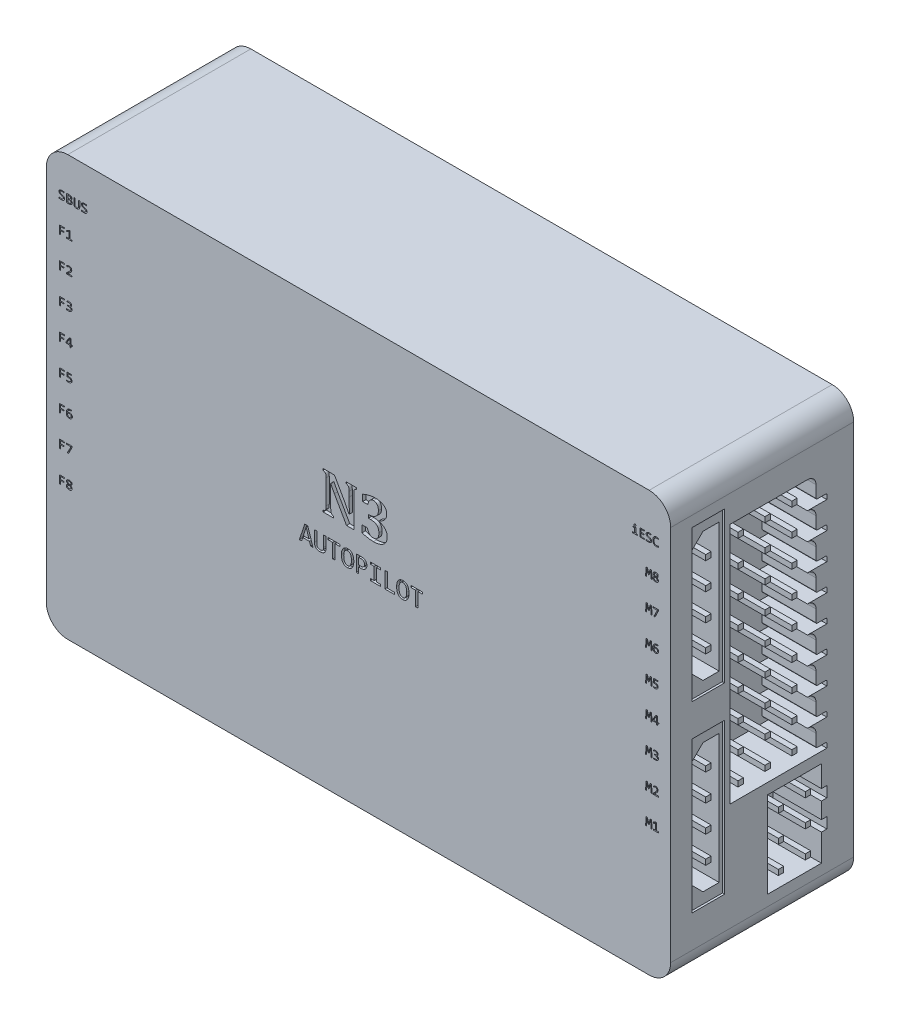
SolidWorks part; units mm, degrees
ref_plane "前视基准面" through (0, 0, 0) normal (0, 0, 1) x (1, 0, 0)
ref_plane "上视基准面" through (0, 0, 0) normal (0, 1, 0) x (1, 0, 0)
ref_plane "右视基准面" through (0, 0, 0) normal (1, 0, 0) x (0, 0, -1)
sketch "Main" plane through (0, 0, 0) normal (0, 0, 1) x (1, 0, 0)
  line L0 (-29, 17.5) -> (-29, -17.5)
  line L1 (0, 0) -> (30.1154, 0) construction
  line L2 (0, -7.3749) -> (0, 9.6594) construction
  line L3 (-27, 19.5) -> (27, 19.5)
  line L4 (29, 17.5) -> (29, -17.5)
  line L5 (-27, -19.5) -> (27, -19.5)
  arc A0 (-29, 17.5) -> (-27, 19.5) centre (-27, 17.5) cw
  arc A1 (29, 17.5) -> (27, 19.5) centre (27, 17.5) ccw
  arc A2 (29, -17.5) -> (27, -19.5) centre (27, -17.5) cw
  arc A3 (-29, -17.5) -> (-27, -19.5) centre (-27, -17.5) ccw
  point P6 (-29, 0)
  point P12 (0, 19.5)
  dimension "D2" = 2
  dimension "D1" = 29
  dimension "D4" = 19.5
extrude "Main_P" add sketch "Main" along normal mid plane 17
sketch "草图3" plane through (0, 0, 8.5) normal (0, 0, 1) x (1, 0, 0)
  line L0 (0, 0) -> (18.2534, 0) construction
  line L1 (0, 0) -> (0, 13.6083) construction
  text T0 "N3" font "Cambria" height 3.5
  text T1 "AUTOPILOT" font "Consolas" height 1.5
  dimension "D1" = 3.55
  dimension "D2" = 5.5
extrude "Font" cut sketch "草图3" against normal blind 0.3
sketch "PAM_Interface" plane through (-29, 0, 0) normal (-1, 0, 0) x (0, 0, 1)
  line L0 (-15.3995, 0) -> (15.3995, 0) construction
  line L1 (0, 21.507) -> (0, -21.507) construction
  line L2 (-2.9542, 2.4634) -> (6.0458, 2.4634)
  line L3 (2.0458, 1.7134) -> (2.0458, 0.7134)
  line L4 (6.0458, 2.4634) -> (6.0458, -0.0366)
  line L5 (6.0458, -0.0366) -> (-1.6542, -0.0366)
  line L6 (-2.8542, 1.9634) -> (-2.0542, 1.9634)
  line L7 (-2.9542, 2.4634) -> (-2.9542, 2.0634)
  line L8 (4.5458, 1.7134) -> (5.5458, 1.7134)
  line L9 (-1.9542, 1.8634) -> (-1.9542, 0.2634)
  line L10 (4.5458, 1.7134) -> (4.5458, 0.7134)
  line L11 (4.5458, 0.7134) -> (5.5458, 0.7134)
  line L12 (5.5458, 1.7134) -> (5.5458, 0.7134)
  line L13 (2.0458, 1.7134) -> (3.0458, 1.7134)
  line L14 (3.0458, 1.7134) -> (3.0458, 0.7134)
  line L15 (2.0458, 0.7134) -> (3.0458, 0.7134)
  line L16 (-0.4542, 1.7134) -> (-0.4542, 0.7134)
  line L17 (-0.4542, 1.7134) -> (0.5458, 1.7134)
  line L18 (0.5458, 1.7134) -> (0.5458, 0.7134)
  line L19 (-0.4542, 0.7134) -> (0.5458, 0.7134)
  arc A0 (-2.9542, 2.0634) -> (-2.8542, 1.9634) centre (-2.8542, 2.0634) ccw
  arc A1 (-1.6542, -0.0366) -> (-1.9542, 0.2634) centre (-1.6542, 0.2634) cw
  arc A2 (-1.9542, 1.8634) -> (-2.0542, 1.9634) centre (-2.0542, 1.8634) ccw
  dimension "D3" = 2.5
  dimension "D4" = 0.3
  dimension "D1" = 0.1
  dimension "D5" = 0.1
  dimension "D2" = 0.5
  dimension "D6" = 1
  dimension "D7" = 1
  dimension "D8" = 0.75
  dimension "D9" = 0.5
  dimension "D10" = 8
  dimension "D11" = 3
sketch "SBus" plane through (-29, 0, 0) normal (-1, 0, 0) x (0, 0, 1)
  line L0 (8.5, 9.91) -> (8.5, 21.1586) construction
  line L1 (-7.8997, 19.5) -> (7.3159, 19.5) construction
  line B0 (-6, 16.5) -> (3, 16.5)
  line B1 (3, 16.5) -> (3, 14)
  line B2 (3, 14) -> (-4.2, 14)
  line B3 (-5.9, 16) -> (-5.1, 16)
  line B4 (-6, 16.5) -> (-6, 16.1)
  line B5 (1.75, 15.5) -> (2.25, 15.5)
  line B6 (-5, 15.9) -> (-5, 14.8)
  line B7 (1.75, 15.5) -> (1.75, 15)
  line B8 (1.75, 15) -> (2.25, 15)
  line B9 (2.25, 15.5) -> (2.25, 15)
  line B10 (-0.75, 15.5) -> (-0.25, 15.5)
  line B11 (-0.25, 15.5) -> (-0.25, 15)
  line B12 (-0.75, 15) -> (-0.25, 15)
  line B13 (-0.75, 15.5) -> (-0.75, 15)
  line B14 (-3.25, 15.5) -> (-2.75, 15.5)
  line B15 (-2.75, 15.5) -> (-2.75, 15)
  line B16 (-3.25, 15) -> (-2.75, 15)
  line B17 (-3.25, 15.5) -> (-3.25, 15)
  line B18 (1.75, 15.5) -> (-0.75, 15.5) construction
  line B19 (-6, 14) -> (3, 14)
  line B20 (3, 14) -> (3, 11.5)
  line B21 (3, 11.5) -> (-4.2, 11.5)
  line B22 (-5, 13.4) -> (-5, 12.3)
  line B23 (-5.9, 13.5) -> (-5.1, 13.5)
  line B24 (-6, 14) -> (-6, 13.6)
  line B25 (-3.25, 13) -> (-2.75, 13)
  line B26 (-2.75, 13) -> (-2.75, 12.5)
  line B27 (-3.25, 12.5) -> (-2.75, 12.5)
  line B28 (-3.25, 13) -> (-3.25, 12.5)
  line B29 (-0.75, 13) -> (-0.25, 13)
  line B30 (-0.25, 13) -> (-0.25, 12.5)
  line B31 (-0.75, 12.5) -> (-0.25, 12.5)
  line B32 (-0.75, 13) -> (-0.75, 12.5)
  line B33 (1.75, 13) -> (2.25, 13)
  line B34 (2.25, 13) -> (2.25, 12.5)
  line B35 (1.75, 12.5) -> (2.25, 12.5)
  line B36 (1.75, 13) -> (1.75, 12.5)
  line B37 (-6, 11.5) -> (3, 11.5)
  line B38 (3, 11.5) -> (3, 9)
  line B39 (3, 9) -> (-4.2, 9)
  line B40 (-5, 10.9) -> (-5, 9.8)
  line B41 (-5.9, 11) -> (-5.1, 11)
  line B42 (-6, 11.5) -> (-6, 11.1)
  line B43 (-3.25, 10.5) -> (-2.75, 10.5)
  line B44 (-2.75, 10.5) -> (-2.75, 10)
  line B45 (-3.25, 10) -> (-2.75, 10)
  line B46 (-3.25, 10.5) -> (-3.25, 10)
  line B47 (-0.75, 10.5) -> (-0.25, 10.5)
  line B48 (-0.25, 10.5) -> (-0.25, 10)
  line B49 (-0.75, 10) -> (-0.25, 10)
  line B50 (-0.75, 10.5) -> (-0.75, 10)
  line B51 (1.75, 10.5) -> (2.25, 10.5)
  line B52 (2.25, 10.5) -> (2.25, 10)
  line B53 (1.75, 10) -> (2.25, 10)
  line B54 (1.75, 10.5) -> (1.75, 10)
  line B55 (-6, 9) -> (3, 9)
  line B56 (3, 9) -> (3, 6.5)
  line B57 (3, 6.5) -> (-4.2, 6.5)
  line B58 (-5, 8.4) -> (-5, 7.3)
  line B59 (-5.9, 8.5) -> (-5.1, 8.5)
  line B60 (-6, 9) -> (-6, 8.6)
  line B61 (-3.25, 8) -> (-2.75, 8)
  line B62 (-2.75, 8) -> (-2.75, 7.5)
  line B63 (-3.25, 7.5) -> (-2.75, 7.5)
  line B64 (-3.25, 8) -> (-3.25, 7.5)
  line B65 (-0.75, 8) -> (-0.25, 8)
  line B66 (-0.25, 8) -> (-0.25, 7.5)
  line B67 (-0.75, 7.5) -> (-0.25, 7.5)
  line B68 (-0.75, 8) -> (-0.75, 7.5)
  line B69 (1.75, 8) -> (2.25, 8)
  line B70 (2.25, 8) -> (2.25, 7.5)
  line B71 (1.75, 7.5) -> (2.25, 7.5)
  line B72 (1.75, 8) -> (1.75, 7.5)
  line B73 (-6, 6.5) -> (3, 6.5)
  line B74 (3, 6.5) -> (3, 4)
  line B75 (3, 4) -> (-4.2, 4)
  line B76 (-5, 5.9) -> (-5, 4.8)
  line B77 (-5.9, 6) -> (-5.1, 6)
  line B78 (-6, 6.5) -> (-6, 6.1)
  line B79 (-3.25, 5.5) -> (-2.75, 5.5)
  line B80 (-2.75, 5.5) -> (-2.75, 5)
  line B81 (-3.25, 5) -> (-2.75, 5)
  line B82 (-3.25, 5.5) -> (-3.25, 5)
  line B83 (-0.75, 5.5) -> (-0.25, 5.5)
  line B84 (-0.25, 5.5) -> (-0.25, 5)
  line B85 (-0.75, 5) -> (-0.25, 5)
  line B86 (-0.75, 5.5) -> (-0.75, 5)
  line B87 (1.75, 5.5) -> (2.25, 5.5)
  line B88 (2.25, 5.5) -> (2.25, 5)
  line B89 (1.75, 5) -> (2.25, 5)
  line B90 (1.75, 5.5) -> (1.75, 5)
  line B91 (-6, 4) -> (3, 4)
  line B92 (3, 4) -> (3, 1.5)
  line B93 (3, 1.5) -> (-4.2, 1.5)
  line B94 (-5, 3.4) -> (-5, 2.3)
  line B95 (-5.9, 3.5) -> (-5.1, 3.5)
  line B96 (-6, 4) -> (-6, 3.6)
  line B97 (-3.25, 3) -> (-2.75, 3)
  line B98 (-2.75, 3) -> (-2.75, 2.5)
  line B99 (-3.25, 2.5) -> (-2.75, 2.5)
  line B100 (-3.25, 3) -> (-3.25, 2.5)
  line B101 (-0.75, 3) -> (-0.25, 3)
  line B102 (-0.25, 3) -> (-0.25, 2.5)
  line B103 (-0.75, 2.5) -> (-0.25, 2.5)
  line B104 (-0.75, 3) -> (-0.75, 2.5)
  line B105 (1.75, 3) -> (2.25, 3)
  line B106 (2.25, 3) -> (2.25, 2.5)
  line B107 (1.75, 2.5) -> (2.25, 2.5)
  line B108 (1.75, 3) -> (1.75, 2.5)
  line B109 (-6, 1.5) -> (3, 1.5)
  line B110 (3, 1.5) -> (3, -1)
  line B111 (3, -1) -> (-4.2, -1)
  line B112 (-5, 0.9) -> (-5, -0.2)
  line B113 (-5.9, 1) -> (-5.1, 1)
  line B114 (-6, 1.5) -> (-6, 1.1)
  line B115 (-3.25, 0.5) -> (-2.75, 0.5)
  line B116 (-2.75, 0.5) -> (-2.75, 0)
  line B117 (-3.25, 0) -> (-2.75, 0)
  line B118 (-3.25, 0.5) -> (-3.25, 0)
  line B119 (-0.75, 0.5) -> (-0.25, 0.5)
  line B120 (-0.25, 0.5) -> (-0.25, 0)
  line B121 (-0.75, 0) -> (-0.25, 0)
  line B122 (-0.75, 0.5) -> (-0.75, 0)
  line B123 (1.75, 0.5) -> (2.25, 0.5)
  line B124 (2.25, 0.5) -> (2.25, 0)
  line B125 (1.75, 0) -> (2.25, 0)
  line B126 (1.75, 0.5) -> (1.75, 0)
  line B127 (-6, -1) -> (3, -1)
  line B128 (3, -1) -> (3, -3.5)
  line B129 (3, -3.5) -> (-4.2, -3.5)
  line B130 (-5, -1.6) -> (-5, -2.7)
  line B131 (-5.9, -1.5) -> (-5.1, -1.5)
  line B132 (-6, -1) -> (-6, -1.4)
  line B133 (-3.25, -2) -> (-2.75, -2)
  line B134 (-2.75, -2) -> (-2.75, -2.5)
  line B135 (-3.25, -2.5) -> (-2.75, -2.5)
  line B136 (-3.25, -2) -> (-3.25, -2.5)
  line B137 (-0.75, -2) -> (-0.25, -2)
  line B138 (-0.25, -2) -> (-0.25, -2.5)
  line B139 (-0.75, -2.5) -> (-0.25, -2.5)
  line B140 (-0.75, -2) -> (-0.75, -2.5)
  line B141 (1.75, -2) -> (2.25, -2)
  line B142 (2.25, -2) -> (2.25, -2.5)
  line B143 (1.75, -2.5) -> (2.25, -2.5)
  line B144 (1.75, -2) -> (1.75, -2.5)
  line B145 (-6, -3.5) -> (3, -3.5)
  line B146 (3, -3.5) -> (3, -6)
  line B147 (3, -6) -> (-4.2, -6)
  line B148 (-5, -4.1) -> (-5, -5.2)
  line B149 (-5.9, -4) -> (-5.1, -4)
  line B150 (-6, -3.5) -> (-6, -3.9)
  line B151 (-3.25, -4.5) -> (-2.75, -4.5)
  line B152 (-2.75, -4.5) -> (-2.75, -5)
  line B153 (-3.25, -5) -> (-2.75, -5)
  line B154 (-3.25, -4.5) -> (-3.25, -5)
  line B155 (-0.75, -4.5) -> (-0.25, -4.5)
  line B156 (-0.25, -4.5) -> (-0.25, -5)
  line B157 (-0.75, -5) -> (-0.25, -5)
  line B158 (-0.75, -4.5) -> (-0.75, -5)
  line B159 (1.75, -4.5) -> (2.25, -4.5)
  line B160 (2.25, -4.5) -> (2.25, -5)
  line B161 (1.75, -5) -> (2.25, -5)
  line B162 (1.75, -4.5) -> (1.75, -5)
  line B163 (-6, 16.5) -> (-6, 14) construction
  arc B164 (-6, 16.1) -> (-5.9, 16) centre (-5.9, 16.1) ccw
  arc B165 (-4.2, 14) -> (-5, 14.8) centre (-4.2, 14.8) cw
  arc B166 (-5, 15.9) -> (-5.1, 16) centre (-5.1, 15.9) ccw
  arc B167 (-4.2, 11.5) -> (-5, 12.3) centre (-4.2, 12.3) cw
  arc B168 (-5, 13.4) -> (-5.1, 13.5) centre (-5.1, 13.4) ccw
  arc B169 (-6, 13.6) -> (-5.9, 13.5) centre (-5.9, 13.6) ccw
  arc B170 (-4.2, 9) -> (-5, 9.8) centre (-4.2, 9.8) cw
  arc B171 (-5, 10.9) -> (-5.1, 11) centre (-5.1, 10.9) ccw
  arc B172 (-6, 11.1) -> (-5.9, 11) centre (-5.9, 11.1) ccw
  arc B173 (-4.2, 6.5) -> (-5, 7.3) centre (-4.2, 7.3) cw
  arc B174 (-5, 8.4) -> (-5.1, 8.5) centre (-5.1, 8.4) ccw
  arc B175 (-6, 8.6) -> (-5.9, 8.5) centre (-5.9, 8.6) ccw
  arc B176 (-4.2, 4) -> (-5, 4.8) centre (-4.2, 4.8) cw
  arc B177 (-5, 5.9) -> (-5.1, 6) centre (-5.1, 5.9) ccw
  arc B178 (-6, 6.1) -> (-5.9, 6) centre (-5.9, 6.1) ccw
  arc B179 (-4.2, 1.5) -> (-5, 2.3) centre (-4.2, 2.3) cw
  arc B180 (-5, 3.4) -> (-5.1, 3.5) centre (-5.1, 3.4) ccw
  arc B181 (-6, 3.6) -> (-5.9, 3.5) centre (-5.9, 3.6) ccw
  arc B182 (-4.2, -1) -> (-5, -0.2) centre (-4.2, -0.2) cw
  arc B183 (-5, 0.9) -> (-5.1, 1) centre (-5.1, 0.9) ccw
  arc B184 (-6, 1.1) -> (-5.9, 1) centre (-5.9, 1.1) ccw
  arc B185 (-4.2, -3.5) -> (-5, -2.7) centre (-4.2, -2.7) cw
  arc B186 (-5, -1.6) -> (-5.1, -1.5) centre (-5.1, -1.6) ccw
  arc B187 (-6, -1.4) -> (-5.9, -1.5) centre (-5.9, -1.4) ccw
  arc B188 (-4.2, -6) -> (-5, -5.2) centre (-4.2, -5.2) cw
  arc B189 (-5, -4.1) -> (-5.1, -4) centre (-5.1, -4.1) ccw
  arc B190 (-6, -3.9) -> (-5.9, -4) centre (-5.9, -3.9) ccw
  dimension "D13" = 3
  dimension "D19" = 5.5
sketch_block_instance "Block_sbus-1"
sketch_block "Block_sbus" parameters "D2"=0.1, "D3"=0.1, "D11"=0.8, "D1"=0.5, "D4"=0.5, "D5"=0.5, "D6"=1, "D7"=9, "D8"=0.75, "D9"=2.5, "D10"=2.5, "D12"=8, "D13"=2.5
extrude "切除-拉伸1" cut sketch "SBus" against normal blind 5 contours B166 B6 B165 B2 B1 B0 B4 B164 B3 B16 B17 B14 B15 B12 B13 B10 B11 B5 B9 B8 B7 | B2 | B42 B172 B41 B171 B40 B170 B39 B38 B21 B37 B54 B51 B52 B53 B50 B47 B48 B49 B46 B43 B44 B45 | B60 B175 B59 B174 B58 B173 B57 B56 B39 B55 B72 B69 B70 B71 B68 B65 B66 B67 B64 B61 B62 B63 | B78 B178 B77 B177 B76 B176 B75 B74 B57 B73 B90 B87 B88 B89 B86 B83 B84 B85 B82 B79 B80 B81 | B96 B181 B95 B180 B94 B179 B93 B92 B75 B91 B108 B105 B106 B107 B104 B101 B102 B103 B100 B97 B98 B99 | B114 B184 B113 B183 B112 B182 B111 B110 B93 B109 B126 B123 B124 B125 B122 B119 B120 B121 B118 B115 B116 B117 | B132 B187 B131 B186 B130 B185 B129 B128 B111 B127 B144 B141 B142 B143 B140 B137 B138 B139 B136 B133 B134 B135 | B150 B190 B149 B189 B148 B188 B147 B146 B129 B145 B154 B151 B152 B153 B158 B155 B156 B157 B162 B159 B160 B161 region at (-29, 15.283, -1.107) region at (-29, 12.783, -1.107) region at (-29, 10.283, -1.107) region at (-29, 7.783, -1.107) region at (-29, 5.283, -1.107) region at (-29, 2.783, -1.107) region at (-29, 0.283, -1.107) region at (-29, -2.217, -1.107) region at (-29, -4.717, -1.107)
sketch "Can" plane through (-29, 0, 0) normal (-1, 0, 0) x (0, 0, -1)
  line L0 (-5.3, 8.5782) -> (-5.3, -20.5135) construction
  line L1 (0.6525, -7.5) -> (-13.2525, -7.5) construction
  line L2 (-3.8, -13.5) -> (-3.8, -1.5)
  line L3 (-6.3, -12.5) -> (-6.3, -2.5)
  line L4 (-3.8, -13.5) -> (-5.3, -13.5)
  line L5 (-3.8, -1.5) -> (-5.3, -1.5)
  line L6 (-6.3, -12.5) -> (-5.3, -13.5)
  line L7 (-6.3, -2.5) -> (-5.3, -1.5)
  line L8 (-3.8, 3.5) -> (-3.8, 15.5)
  line L9 (-6.5, -14.5) -> (-3.5, -14.5)
  line L10 (-3.5, -14.5) -> (-3.5, -0.5)
  line L11 (-3.5, -0.5) -> (-6.5, -0.5)
  line L12 (-6.5, -0.5) -> (-6.5, -14.5)
  line L13 (-5.05, -6.5) -> (-4.55, -6.5)
  line L14 (-5.05, -4) -> (-5.05, -3.5)
  line L15 (-5.05, -4) -> (-4.55, -4)
  line L16 (-4.55, -4) -> (-4.55, -3.5)
  line L17 (-5.05, -3.5) -> (-4.55, -3.5)
  line L18 (-5.05, -6.5) -> (-5.05, -6)
  line L19 (-5.05, -6) -> (-4.55, -6)
  line L20 (-4.55, -6.5) -> (-4.55, -6)
  line L21 (-5.05, -9) -> (-4.55, -9)
  line L22 (-5.05, -9) -> (-5.05, -8.5)
  line L23 (-5.05, -8.5) -> (-4.55, -8.5)
  line L24 (-4.55, -9) -> (-4.55, -8.5)
  line L25 (-5.05, -11.5) -> (-4.55, -11.5)
  line L26 (-5.05, -11.5) -> (-5.05, -11)
  line L27 (-5.05, -11) -> (-4.55, -11)
  line L28 (-4.55, -11.5) -> (-4.55, -11)
  line L29 (-5.05, -4) -> (-5.05, -6.5) construction
  line L30 (-8.5, 5.7095) -> (-8.5, -22.0792) construction
  line L31 (-6.3, 4.5) -> (-6.3, 14.5)
  line L32 (-1.0449, -19.5) -> (-15.4243, -19.5) construction
  line L33 (-3.8, 3.5) -> (-5.3, 3.5)
  line L34 (-3.8, 15.5) -> (-5.3, 15.5)
  line L35 (-6.3, 4.5) -> (-5.3, 3.5)
  line L36 (-6.3, 14.5) -> (-5.3, 15.5)
  line L37 (-6.5, 2.5) -> (-3.5, 2.5)
  line L38 (-3.5, 2.5) -> (-3.5, 16.5)
  line L39 (-3.5, 16.5) -> (-6.5, 16.5)
  line L40 (-6.5, 16.5) -> (-6.5, 2.5)
  line L41 (-5.05, 10.5) -> (-4.55, 10.5)
  line L42 (-5.05, 13) -> (-5.05, 13.5)
  line L43 (-5.05, 13) -> (-4.55, 13)
  line L44 (-4.55, 13) -> (-4.55, 13.5)
  line L45 (-5.05, 13.5) -> (-4.55, 13.5)
  line L46 (-5.05, 10.5) -> (-5.05, 11)
  line L47 (-5.05, 11) -> (-4.55, 11)
  line L48 (-4.55, 10.5) -> (-4.55, 11)
  line L49 (-5.05, 8) -> (-4.55, 8)
  line L50 (-5.05, 8) -> (-5.05, 8.5)
  line L51 (-5.05, 8.5) -> (-4.55, 8.5)
  line L52 (-4.55, 8) -> (-4.55, 8.5)
  line L53 (-5.05, 5.5) -> (-4.55, 5.5)
  line L54 (-5.05, 5.5) -> (-5.05, 6)
  line L55 (-5.05, 6) -> (-4.55, 6)
  line L56 (-4.55, 5.5) -> (-4.55, 6)
  line L57 (-5.3, 25.5782) -> (-5.3, -3.5135) construction
  line L58 (0.6525, 9.5) -> (-13.2525, 9.5) construction
  line L59 (-5.05, 13) -> (-5.05, 10.5) construction
  line L60 (-3.8, -13.5) -> (-3.8, 3.5) construction
  point P7 (-3.8, -7.5)
  point P10 (-6.3, -7.5)
  point P15 (-4.55, -1.5)
  dimension "D1" = 12
  dimension "D2" = 10
  dimension "D3" = 2.5
  dimension "D4" = 1.5
  dimension "D5" = 5
  dimension "D6" = 14
  dimension "D7" = 3
  dimension "D8" = 7
  dimension "D9" = 0.2
  dimension "D10" = 0.5
  dimension "D11" = 0.5
  dimension "D12" = 2.5
  dimension "D13" = 0.75
  dimension "D15" = 2.5
  dimension "D16" = 2
  dimension "D17" = 45
  dimension "D18" = 2
  dimension "D19" = 1
  dimension "D21" = 17
  dimension "D14" = 4
  dimension "D20" = 2
extrude "切除-拉伸2" cut sketch "Can" against normal blind 0.2 contours L11 L12 L9 L10 L3 L7 L5 L2 L4 L6 | L39 L40 L37 L38 L31 L36 L34 L8 L33 L35 | L25 L28 L27 L26 | L21 L24 L23 L22 | L13 L20 L19 L18 | L17 L14 L15 L16 | L53 L56 L55 L54 | L49 L52 L51 L50 | L25 L28 L27 L26 | L21 L24 L23 L22 | L13 L20 L19 L18 | L15 L14 L17 L16 | L53 L56 L55 L54 | L50 L51 L52 L49 | L41 L48 L47 L46 | L44 L45 L42 L43 region at (-29, 7.5, 6.3568) region at (-29, 6.25, 4.8) region at (-29, 3.75, 4.8) region at (-29, 8.75, 4.8) region at (-29, 11.25, 4.8) region at (-29, -9.5, 6.3568) region at (-29, -8.25, 4.8) region at (-29, -5.75, 4.8)
extrude "切除-拉伸3" cut sketch "草图8<6>" against normal blind 5 contours L7 L3 L6 L4 L2 L5 L28 L25 L26 L27 L24 L21 L22 L23 L20 L13 L18 L19 L14 L17 L16 L15 | L36 L31 L35 L33 L8 L34 L56 L53 L54 L55 L52 L49 L50 L51 L48 L41 L46 L47 L42 L45 L44 L43 region at (-29, 7.5, 5.0262) region at (-29, -9.5, 5.0262)
sketch "草图8<6>" plane through (-29, 0, 0) normal (-1, 0, 0) x (0, 0, -1) same geometry as "Can"
sketch "草图10" plane through (29, 0, 0) normal (1, 0, 0) x (0, 0, -1)
  line L0 (-3.5, -14.5) -> (-3.5, 2.5) construction
  line B0 (-3.8, -13.5) -> (-3.8, -1.5)
  line B1 (-6.3, -12.5) -> (-6.3, -2.5)
  line B2 (-3.8, -13.5) -> (-5.3, -13.5)
  line B3 (-3.8, -1.5) -> (-5.3, -1.5)
  line B4 (-6.3, -12.5) -> (-5.3, -13.5)
  line B5 (-6.3, -2.5) -> (-5.3, -1.5)
  line B6 (-6.5, -14.5) -> (-3.5, -14.5)
  line B7 (-3.5, -14.5) -> (-3.5, -0.5)
  line B8 (-3.5, -0.5) -> (-6.5, -0.5)
  line B9 (-6.5, -0.5) -> (-6.5, -14.5)
  line B10 (-5.05, -6.5) -> (-4.55, -6.5)
  line B11 (-5.05, -4) -> (-5.05, -3.5)
  line B12 (-5.05, -4) -> (-4.55, -4)
  line B13 (-4.55, -4) -> (-4.55, -3.5)
  line B14 (-5.05, -3.5) -> (-4.55, -3.5)
  line B15 (-5.05, -6.5) -> (-5.05, -6)
  line B16 (-5.05, -6) -> (-4.55, -6)
  line B17 (-4.55, -6.5) -> (-4.55, -6)
  line B18 (-5.05, -9) -> (-4.55, -9)
  line B19 (-5.05, -9) -> (-5.05, -8.5)
  line B20 (-5.05, -8.5) -> (-4.55, -8.5)
  line B21 (-4.55, -9) -> (-4.55, -8.5)
  line B22 (-5.05, -11.5) -> (-4.55, -11.5)
  line B23 (-5.05, -11.5) -> (-5.05, -11)
  line B24 (-5.05, -11) -> (-4.55, -11)
  line B25 (-4.55, -11.5) -> (-4.55, -11)
  line B26 (-3.8, 3.5) -> (-3.8, 15.5)
  line B27 (-6.3, 4.5) -> (-6.3, 14.5)
  line B28 (-3.8, 3.5) -> (-5.3, 3.5)
  line B29 (-3.8, 15.5) -> (-5.3, 15.5)
  line B30 (-6.3, 4.5) -> (-5.3, 3.5)
  line B31 (-6.3, 14.5) -> (-5.3, 15.5)
  line B32 (-6.5, 2.5) -> (-3.5, 2.5)
  line B33 (-3.5, 2.5) -> (-3.5, 16.5)
  line B34 (-3.5, 16.5) -> (-6.5, 16.5)
  line B35 (-6.5, 16.5) -> (-6.5, 2.5)
  line B36 (-5.05, 10.5) -> (-4.55, 10.5)
  line B37 (-5.05, 13) -> (-5.05, 13.5)
  line B38 (-5.05, 13) -> (-4.55, 13)
  line B39 (-4.55, 13) -> (-4.55, 13.5)
  line B40 (-5.05, 13.5) -> (-4.55, 13.5)
  line B41 (-5.05, 10.5) -> (-5.05, 11)
  line B42 (-5.05, 11) -> (-4.55, 11)
  line B43 (-4.55, 10.5) -> (-4.55, 11)
  line B44 (-5.05, 8) -> (-4.55, 8)
  line B45 (-5.05, 8) -> (-5.05, 8.5)
  line B46 (-5.05, 8.5) -> (-4.55, 8.5)
  line B47 (-4.55, 8) -> (-4.55, 8.5)
  line B48 (-5.05, 5.5) -> (-4.55, 5.5)
  line B49 (-5.05, 5.5) -> (-5.05, 6)
  line B50 (-5.05, 6) -> (-4.55, 6)
  line B51 (-4.55, 5.5) -> (-4.55, 6)
  dimension "D1" = 6.5
  dimension "D2" = 2
  dimension "D3" = 17
  dimension "D4" = 14.5
sketch_block_instance "Can_block-1"
sketch_block "Can_block" parameters "D1"=12, "D2"=10, "D3"=2.5, "D4"=14, "D5"=3, "D6"=0.2, "D7"=0.5, "D8"=0.5, "D9"=2.5, "D10"=0.75, "D11"=2.5, "D12"=2
sketch_block_instance "Can_block-2"
extrude "切除-拉伸4" cut sketch "草图10" against normal blind 0.2 contours B34 B35 B32 B33 B27 B31 B29 B26 B28 B30 | B8 B9 B6 B7 B1 B5 B3 B0 B2 B4 | B40 B37 B38 B39 | B36 B43 B42 B41 | B44 B47 B46 B45 | B48 B51 B50 B49 | B14 B11 B12 B13 | B10 B17 B16 B15 | B18 B21 B20 B19 | B22 B25 B24 B23 region at (29, -7.5, 6.3568) region at (29, -6.25, 4.8) region at (29, -3.75, 4.8) region at (29, -8.75, 4.8) region at (29, -11.25, 4.8) region at (29, 9.5, 6.3568) region at (29, 10.75, 4.8) region at (29, 13.25, 4.8) region at (29, 8.25, 4.8) region at (29, 5.75, 4.8)
extrude "切除-拉伸5" cut sketch "草图10<4>" against normal blind 5 contours B5 B1 B4 B2 B0 B3 B25 B22 B23 B24 B21 B18 B19 B20 B17 B10 B15 B16 B11 B14 B13 B12 | B31 B27 B30 B28 B26 B29 B51 B48 B49 B50 B47 B44 B45 B46 B43 B36 B41 B42 B37 B40 B39 B38 region at (29, -7.5, 5.0262) region at (29, 9.5, 5.0262)
sketch "草图10<4>" plane through (29, 0, 0) normal (1, 0, 0) x (0, 0, -1) same geometry as "草图10"
sketch "草图13" plane through (29, 0, 0) normal (1, 0, 0) x (0, 0, -1)
  line B0 (6, -7.5) -> (-3, -7.5)
  line B1 (-3, -7.5) -> (-3, -5)
  line B2 (-3, -5) -> (4.2, -5)
  line B3 (5.9, -7) -> (5.1, -7)
  line B4 (6, -7.5) -> (6, -7.1)
  line B5 (-1.75, -6.5) -> (-2.25, -6.5)
  line B6 (5, -6.9) -> (5, -5.8)
  line B7 (-1.75, -6.5) -> (-1.75, -6)
  line B8 (-1.75, -6) -> (-2.25, -6)
  line B9 (-2.25, -6.5) -> (-2.25, -6)
  line B10 (0.75, -6.5) -> (0.25, -6.5)
  line B11 (0.25, -6.5) -> (0.25, -6)
  line B12 (0.75, -6) -> (0.25, -6)
  line B13 (0.75, -6.5) -> (0.75, -6)
  line B14 (3.25, -6.5) -> (2.75, -6.5)
  line B15 (2.75, -6.5) -> (2.75, -6)
  line B16 (3.25, -6) -> (2.75, -6)
  line B17 (3.25, -6.5) -> (3.25, -6)
  line B18 (-1.75, -6.5) -> (0.75, -6.5) construction
  line B19 (6, -5) -> (-3, -5)
  line B20 (-3, -5) -> (-3, -2.5)
  line B21 (-3, -2.5) -> (4.2, -2.5)
  line B22 (5, -4.4) -> (5, -3.3)
  line B23 (5.9, -4.5) -> (5.1, -4.5)
  line B24 (6, -5) -> (6, -4.6)
  line B25 (3.25, -4) -> (2.75, -4)
  line B26 (2.75, -4) -> (2.75, -3.5)
  line B27 (3.25, -3.5) -> (2.75, -3.5)
  line B28 (3.25, -4) -> (3.25, -3.5)
  line B29 (0.75, -4) -> (0.25, -4)
  line B30 (0.25, -4) -> (0.25, -3.5)
  line B31 (0.75, -3.5) -> (0.25, -3.5)
  line B32 (0.75, -4) -> (0.75, -3.5)
  line B33 (-1.75, -4) -> (-2.25, -4)
  line B34 (-2.25, -4) -> (-2.25, -3.5)
  line B35 (-1.75, -3.5) -> (-2.25, -3.5)
  line B36 (-1.75, -4) -> (-1.75, -3.5)
  line B37 (6, -2.5) -> (-3, -2.5)
  line B38 (-3, -2.5) -> (-3, 0)
  line B39 (-3, 0) -> (4.2, 0)
  line B40 (5, -1.9) -> (5, -0.8)
  line B41 (5.9, -2) -> (5.1, -2)
  line B42 (6, -2.5) -> (6, -2.1)
  line B43 (3.25, -1.5) -> (2.75, -1.5)
  line B44 (2.75, -1.5) -> (2.75, -1)
  line B45 (3.25, -1) -> (2.75, -1)
  line B46 (3.25, -1.5) -> (3.25, -1)
  line B47 (0.75, -1.5) -> (0.25, -1.5)
  line B48 (0.25, -1.5) -> (0.25, -1)
  line B49 (0.75, -1) -> (0.25, -1)
  line B50 (0.75, -1.5) -> (0.75, -1)
  line B51 (-1.75, -1.5) -> (-2.25, -1.5)
  line B52 (-2.25, -1.5) -> (-2.25, -1)
  line B53 (-1.75, -1) -> (-2.25, -1)
  line B54 (-1.75, -1.5) -> (-1.75, -1)
  line B55 (6, 0) -> (-3, 0)
  line B56 (-3, 0) -> (-3, 2.5)
  line B57 (-3, 2.5) -> (4.2, 2.5)
  line B58 (5, 0.6) -> (5, 1.7)
  line B59 (5.9, 0.5) -> (5.1, 0.5)
  line B60 (6, 0) -> (6, 0.4)
  line B61 (3.25, 1) -> (2.75, 1)
  line B62 (2.75, 1) -> (2.75, 1.5)
  line B63 (3.25, 1.5) -> (2.75, 1.5)
  line B64 (3.25, 1) -> (3.25, 1.5)
  line B65 (0.75, 1) -> (0.25, 1)
  line B66 (0.25, 1) -> (0.25, 1.5)
  line B67 (0.75, 1.5) -> (0.25, 1.5)
  line B68 (0.75, 1) -> (0.75, 1.5)
  line B69 (-1.75, 1) -> (-2.25, 1)
  line B70 (-2.25, 1) -> (-2.25, 1.5)
  line B71 (-1.75, 1.5) -> (-2.25, 1.5)
  line B72 (-1.75, 1) -> (-1.75, 1.5)
  line B73 (6, 2.5) -> (-3, 2.5)
  line B74 (-3, 2.5) -> (-3, 5)
  line B75 (-3, 5) -> (4.2, 5)
  line B76 (5, 3.1) -> (5, 4.2)
  line B77 (5.9, 3) -> (5.1, 3)
  line B78 (6, 2.5) -> (6, 2.9)
  line B79 (3.25, 3.5) -> (2.75, 3.5)
  line B80 (2.75, 3.5) -> (2.75, 4)
  line B81 (3.25, 4) -> (2.75, 4)
  line B82 (3.25, 3.5) -> (3.25, 4)
  line B83 (0.75, 3.5) -> (0.25, 3.5)
  line B84 (0.25, 3.5) -> (0.25, 4)
  line B85 (0.75, 4) -> (0.25, 4)
  line B86 (0.75, 3.5) -> (0.75, 4)
  line B87 (-1.75, 3.5) -> (-2.25, 3.5)
  line B88 (-2.25, 3.5) -> (-2.25, 4)
  line B89 (-1.75, 4) -> (-2.25, 4)
  line B90 (-1.75, 3.5) -> (-1.75, 4)
  line B91 (6, 5) -> (-3, 5)
  line B92 (-3, 5) -> (-3, 7.5)
  line B93 (-3, 7.5) -> (4.2, 7.5)
  line B94 (5, 5.6) -> (5, 6.7)
  line B95 (5.9, 5.5) -> (5.1, 5.5)
  line B96 (6, 5) -> (6, 5.4)
  line B97 (3.25, 6) -> (2.75, 6)
  line B98 (2.75, 6) -> (2.75, 6.5)
  line B99 (3.25, 6.5) -> (2.75, 6.5)
  line B100 (3.25, 6) -> (3.25, 6.5)
  line B101 (0.75, 6) -> (0.25, 6)
  line B102 (0.25, 6) -> (0.25, 6.5)
  line B103 (0.75, 6.5) -> (0.25, 6.5)
  line B104 (0.75, 6) -> (0.75, 6.5)
  line B105 (-1.75, 6) -> (-2.25, 6)
  line B106 (-2.25, 6) -> (-2.25, 6.5)
  line B107 (-1.75, 6.5) -> (-2.25, 6.5)
  line B108 (-1.75, 6) -> (-1.75, 6.5)
  line B109 (6, 7.5) -> (-3, 7.5)
  line B110 (-3, 7.5) -> (-3, 10)
  line B111 (-3, 10) -> (4.2, 10)
  line B112 (5, 8.1) -> (5, 9.2)
  line B113 (5.9, 8) -> (5.1, 8)
  line B114 (6, 7.5) -> (6, 7.9)
  line B115 (3.25, 8.5) -> (2.75, 8.5)
  line B116 (2.75, 8.5) -> (2.75, 9)
  line B117 (3.25, 9) -> (2.75, 9)
  line B118 (3.25, 8.5) -> (3.25, 9)
  line B119 (0.75, 8.5) -> (0.25, 8.5)
  line B120 (0.25, 8.5) -> (0.25, 9)
  line B121 (0.75, 9) -> (0.25, 9)
  line B122 (0.75, 8.5) -> (0.75, 9)
  line B123 (-1.75, 8.5) -> (-2.25, 8.5)
  line B124 (-2.25, 8.5) -> (-2.25, 9)
  line B125 (-1.75, 9) -> (-2.25, 9)
  line B126 (-1.75, 8.5) -> (-1.75, 9)
  line B127 (6, 10) -> (-3, 10)
  line B128 (-3, 10) -> (-3, 12.5)
  line B129 (-3, 12.5) -> (4.2, 12.5)
  line B130 (5, 10.6) -> (5, 11.7)
  line B131 (5.9, 10.5) -> (5.1, 10.5)
  line B132 (6, 10) -> (6, 10.4)
  line B133 (3.25, 11) -> (2.75, 11)
  line B134 (2.75, 11) -> (2.75, 11.5)
  line B135 (3.25, 11.5) -> (2.75, 11.5)
  line B136 (3.25, 11) -> (3.25, 11.5)
  line B137 (0.75, 11) -> (0.25, 11)
  line B138 (0.25, 11) -> (0.25, 11.5)
  line B139 (0.75, 11.5) -> (0.25, 11.5)
  line B140 (0.75, 11) -> (0.75, 11.5)
  line B141 (-1.75, 11) -> (-2.25, 11)
  line B142 (-2.25, 11) -> (-2.25, 11.5)
  line B143 (-1.75, 11.5) -> (-2.25, 11.5)
  line B144 (-1.75, 11) -> (-1.75, 11.5)
  line B145 (6, 12.5) -> (-3, 12.5)
  line B146 (-3, 12.5) -> (-3, 15)
  line B147 (-3, 15) -> (4.2, 15)
  line B148 (5, 13.1) -> (5, 14.2)
  line B149 (5.9, 13) -> (5.1, 13)
  line B150 (6, 12.5) -> (6, 12.9)
  line B151 (3.25, 13.5) -> (2.75, 13.5)
  line B152 (2.75, 13.5) -> (2.75, 14)
  line B153 (3.25, 14) -> (2.75, 14)
  line B154 (3.25, 13.5) -> (3.25, 14)
  line B155 (0.75, 13.5) -> (0.25, 13.5)
  line B156 (0.25, 13.5) -> (0.25, 14)
  line B157 (0.75, 14) -> (0.25, 14)
  line B158 (0.75, 13.5) -> (0.75, 14)
  line B159 (-1.75, 13.5) -> (-2.25, 13.5)
  line B160 (-2.25, 13.5) -> (-2.25, 14)
  line B161 (-1.75, 14) -> (-2.25, 14)
  line B162 (-1.75, 13.5) -> (-1.75, 14)
  line B163 (6, -7.5) -> (6, -5) construction
  arc B164 (6, -7.1) -> (5.9, -7) centre (5.9, -7.1) ccw
  arc B165 (4.2, -5) -> (5, -5.8) centre (4.2, -5.8) cw
  arc B166 (5, -6.9) -> (5.1, -7) centre (5.1, -6.9) ccw
  arc B167 (4.2, -2.5) -> (5, -3.3) centre (4.2, -3.3) cw
  arc B168 (5, -4.4) -> (5.1, -4.5) centre (5.1, -4.4) ccw
  arc B169 (6, -4.6) -> (5.9, -4.5) centre (5.9, -4.6) ccw
  arc B170 (4.2, 0) -> (5, -0.8) centre (4.2, -0.8) cw
  arc B171 (5, -1.9) -> (5.1, -2) centre (5.1, -1.9) ccw
  arc B172 (6, -2.1) -> (5.9, -2) centre (5.9, -2.1) ccw
  arc B173 (4.2, 2.5) -> (5, 1.7) centre (4.2, 1.7) cw
  arc B174 (5, 0.6) -> (5.1, 0.5) centre (5.1, 0.6) ccw
  arc B175 (6, 0.4) -> (5.9, 0.5) centre (5.9, 0.4) ccw
  arc B176 (4.2, 5) -> (5, 4.2) centre (4.2, 4.2) cw
  arc B177 (5, 3.1) -> (5.1, 3) centre (5.1, 3.1) ccw
  arc B178 (6, 2.9) -> (5.9, 3) centre (5.9, 2.9) ccw
  arc B179 (4.2, 7.5) -> (5, 6.7) centre (4.2, 6.7) cw
  arc B180 (5, 5.6) -> (5.1, 5.5) centre (5.1, 5.6) ccw
  arc B181 (6, 5.4) -> (5.9, 5.5) centre (5.9, 5.4) ccw
  arc B182 (4.2, 10) -> (5, 9.2) centre (4.2, 9.2) cw
  arc B183 (5, 8.1) -> (5.1, 8) centre (5.1, 8.1) ccw
  arc B184 (6, 7.9) -> (5.9, 8) centre (5.9, 7.9) ccw
  arc B185 (4.2, 12.5) -> (5, 11.7) centre (4.2, 11.7) cw
  arc B186 (5, 10.6) -> (5.1, 10.5) centre (5.1, 10.6) ccw
  arc B187 (6, 10.4) -> (5.9, 10.5) centre (5.9, 10.4) ccw
  arc B188 (4.2, 15) -> (5, 14.2) centre (4.2, 14.2) cw
  arc B189 (5, 13.1) -> (5.1, 13) centre (5.1, 13.1) ccw
  arc B190 (6, 12.9) -> (5.9, 13) centre (5.9, 12.9) ccw
  line M374 (8.5, 17.5) -> (-8.5, 17.5)
  dimension "D1" = 3
  dimension "D3" = 7.5
sketch_block_instance "Block_sbus-2"
extrude "切除-拉伸6" cut sketch "草图13" against normal blind 5 contours B150 B190 B149 B189 B148 B188 B146 B129 B145 B162 B159 B160 B161 B158 B155 B156 B157 B154 B151 B152 B153 M374 | B132 B187 B131 B186 B130 B185 B129 B128 B111 B127 B144 B141 B142 B143 B140 B137 B138 B139 B136 B133 B134 B135 | B114 B184 B113 B183 B112 B182 B111 B110 B93 B109 B126 B123 B124 B125 B122 B119 B120 B121 B118 B115 B116 B117 | B96 B181 B95 B180 B94 B179 B93 B92 B75 B91 B108 B105 B106 B107 B104 B101 B102 B103 B100 B97 B98 B99 | B78 B178 B77 B177 B76 B176 B75 B74 B57 B73 B90 B87 B88 B89 B86 B83 B84 B85 B82 B79 B80 B81 | B60 B175 B59 B174 B58 B173 B57 B56 B39 B55 B72 B69 B70 B71 B68 B65 B66 B67 B64 B61 B62 B63 | B42 B172 B41 B171 B40 B170 B39 B38 B21 B37 B54 B51 B52 B53 B50 B47 B48 B49 B46 B43 B44 B45 | B24 B169 B23 B168 B22 B167 B21 B20 B2 B19 B36 B33 B34 B35 B32 B29 B30 B31 B28 B25 B26 B27 | B166 B6 B165 B2 B1 B0 B4 B164 B3 B17 B14 B15 B16 B13 B10 B11 B12 B5 B9 B8 B7 region at (29, -6.283, -1.107) region at (29, -3.783, -1.107) region at (29, -1.283, -1.107) region at (29, 1.217, -1.107) region at (29, 3.717, -1.107) region at (29, 6.217, -1.107) region at (29, 8.717, -1.107) region at (29, 11.217, -1.107) region at (29, 13.717, -1.107)
sketch "草图14" plane through (29, 0, 0) normal (1, 0, 0) x (0, 0, -1)
  line B0 (0.5, -8.5) -> (5.5, -8.5)
  line B1 (0.5, -8.5) -> (0.5, -16.5)
  line B2 (0.5, -16.5) -> (5.5, -16.5)
  line B3 (5.5, -8.5) -> (5.5, -16.5)
  line B4 (6, -11.5) -> (5.5, -11.5)
  line B5 (6, -11.5) -> (6, -10.5)
  line B6 (6, -10.5) -> (5.5, -10.5)
  line B7 (5.5, -11.5) -> (5.5, -10.5)
  line B8 (6, -14) -> (6, -13)
  line B9 (6, -14) -> (5.5, -14)
  line B10 (5.5, -14) -> (5.5, -13)
  line B11 (6, -13) -> (5.5, -13)
  line B12 (6, -11.5) -> (6, -14) construction
  line B13 (4, -10) -> (4, -10.5)
  line B14 (1.5, -10) -> (2, -10)
  line B15 (1.5, -10) -> (1.5, -10.5)
  line B16 (1.5, -10.5) -> (2, -10.5)
  line B17 (2, -10) -> (2, -10.5)
  line B18 (4, -10) -> (4.5, -10)
  line B19 (4.5, -10) -> (4.5, -10.5)
  line B20 (4, -10.5) -> (4.5, -10.5)
  line B21 (1.5, -10) -> (4, -10) construction
  line B22 (1.5, -12.5) -> (1.5, -13)
  line B23 (1.5, -12.5) -> (2, -12.5)
  line B24 (2, -12.5) -> (2, -13)
  line B25 (1.5, -13) -> (2, -13)
  line B26 (4, -12.5) -> (4, -13)
  line B27 (4, -13) -> (4.5, -13)
  line B28 (4.5, -12.5) -> (4.5, -13)
  line B29 (4, -12.5) -> (4.5, -12.5)
  line B30 (1.5, -15) -> (1.5, -15.5)
  line B31 (1.5, -15) -> (2, -15)
  line B32 (2, -15) -> (2, -15.5)
  line B33 (1.5, -15.5) -> (2, -15.5)
  line B34 (4, -15) -> (4, -15.5)
  line B35 (4, -15.5) -> (4.5, -15.5)
  line B36 (4.5, -15) -> (4.5, -15.5)
  line B37 (4, -15) -> (4.5, -15)
  line B38 (1.5, -10) -> (1.5, -12.5) construction
  dimension "D1" = 16.5
  dimension "D2" = 0.5
sketch_block_instance "块4-1"
sketch_block "块4" parameters "D1"=5, "D2"=8, "D3"=1, "D4"=0.5, "D5"=2, "D6"=2.5, "D7"=0.5, "D8"=0.5, "D9"=1.5, "D10"=1, "D11"=2.5, "D12"=2.5
extrude "切除-拉伸7" cut sketch "草图14" against normal blind 5 contours B3 B0 B1 B2 B33 B30 B31 B32 B25 B22 B23 B24 B20 B13 B18 B19 B14 B17 B16 B15 B26 B29 B28 B27 B34 B37 B36 B35 | B5 B6 B3 B4 | B8 B11 B3 B9 region at (29, -12.4903, -3) region at (29, -11, -5.75) region at (29, -13.5, -5.75)
sketch "草图15" plane through (0, -19.5, 0) normal (0, -1, 0) x (1, 0, 0)
  point P6 (4.6338, 3.0182)
  point P9 (-6.8662, 3.0182)
  point P14 (-6.8662, -2.4818)
  line B0 (1, -0.5) -> (1, -1)
  line B1 (-5.45, 1) -> (5.45, 1)
  line B2 (-5.75, 0.7) -> (-5.75, -4.4)
  line B3 (-5.65, -4.5) -> (5.65, -4.5)
  line B4 (5.75, 0.7) -> (5.75, -4.4)
  line B5 (3.5, -0.5) -> (4, -0.5)
  line B6 (3.5, -0.5) -> (3.5, -1)
  line B7 (3.5, -1) -> (4, -1)
  line B8 (4, -0.5) -> (4, -1)
  line B9 (1, -0.5) -> (1.5, -0.5)
  line B10 (1.5, -0.5) -> (1.5, -1)
  line B11 (1, -1) -> (1.5, -1)
  line B12 (-1.5, -0.5) -> (-1.5, -1)
  line B13 (-1.5, -0.5) -> (-1, -0.5)
  line B14 (-1, -0.5) -> (-1, -1)
  line B15 (-1.5, -1) -> (-1, -1)
  line B16 (-4, -0.5) -> (-4, -1)
  line B17 (-4, -0.5) -> (-3.5, -0.5)
  line B18 (-3.5, -0.5) -> (-3.5, -1)
  line B19 (-4, -1) -> (-3.5, -1)
  line B20 (3.5, -0.5) -> (1, -0.5) construction
  line B21 (3.5, -3) -> (3.5, -3.5)
  line B22 (3.5, -3) -> (4, -3)
  line B23 (4, -3) -> (4, -3.5)
  line B24 (3.5, -3.5) -> (4, -3.5)
  line B25 (1, -3) -> (1, -3.5)
  line B26 (1, -3.5) -> (1.5, -3.5)
  line B27 (1.5, -3) -> (1.5, -3.5)
  line B28 (1, -3) -> (1.5, -3)
  line B29 (-1.5, -3) -> (-1.5, -3.5)
  line B30 (-1.5, -3.5) -> (-1, -3.5)
  line B31 (-1, -3) -> (-1, -3.5)
  line B32 (-1.5, -3) -> (-1, -3)
  line B33 (-4, -3) -> (-4, -3.5)
  line B34 (-4, -3.5) -> (-3.5, -3.5)
  line B35 (-3.5, -3) -> (-3.5, -3.5)
  line B36 (-4, -3) -> (-3.5, -3)
  line B37 (3.5, -0.5) -> (3.5, -3) construction
  arc B38 (5.75, 0.7) -> (5.45, 1) centre (5.45, 0.7) ccw
  arc B39 (-5.75, 0.7) -> (-5.45, 1) centre (-5.45, 0.7) cw
  arc B40 (5.75, -4.4) -> (5.65, -4.5) centre (5.65, -4.4) cw
  arc B41 (-5.65, -4.5) -> (-5.75, -4.4) centre (-5.65, -4.4) cw
  dimension "D3" = 4.5
  dimension "D4" = 5.75
  dimension "D1" = 11.5
  dimension "D2" = 5.5
sketch_block_instance "块5-1"
sketch_block "块5" parameters "D1"=0.3, "D2"=0.1, "D3"=0.5, "D4"=0.5, "D5"=1.75, "D6"=1.5, "D7"=2.5, "D8"=2.5
extrude "切除-拉伸8" cut sketch "草图15" against normal blind 5
sketch "草图16" plane through (0, 0, 8.5) normal (0, 0, 1) x (1, 0, 0)
  text T0 "SBUS\r\nF1\r\nF2\r\nF3\r\nF4\r\nF5\r\nF6\r\nF7\r\nF8" font "Consolas" height 0.75
  text T1 "iESC\r\n  M8\r\n  M7\r\n  M6\r\n  M5\r\n  M4\r\n  M3\r\n  M2\r\n  M1" font "Consolas" height 0.75
extrude "切除-拉伸9" cut sketch "草图16" against normal blind 0.2
